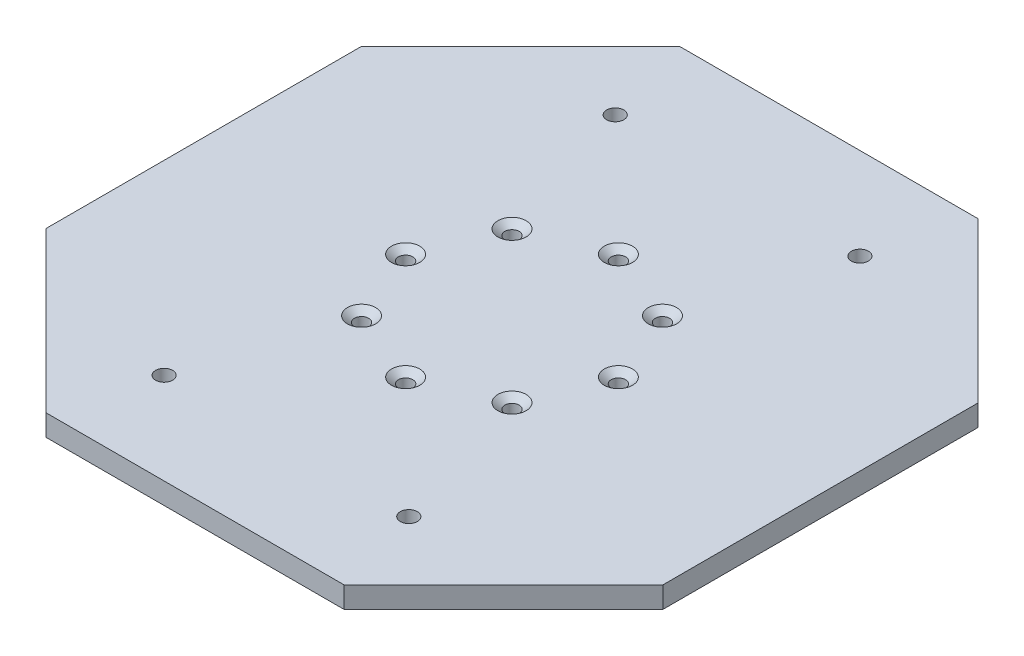
SolidWorks part; units mm, degrees
material "6061-T6 (SS)"
ref_plane "Front Plane" through (0, 0, 0) normal (0, 0, 1) x (1, 0, 0)
ref_plane "Top Plane" through (0, 0, 0) normal (0, 1, 0) x (1, 0, 0)
ref_plane "Right Plane" through (0, 0, 0) normal (1, 0, 0) x (0, 0, -1)
sketch "Sketch1" plane through (0, 0, 0) normal (0, 1, 0) x (1, 0, 0)
  line L0 (-92.075, 46.99) -> (-44.45, 94.615)
  line L1 (-44.45, -94.615) -> (44.45, -94.615)
  line L2 (-92.075, -46.99) -> (-92.075, 46.99)
  line L3 (-44.45, 94.615) -> (44.45, 94.615)
  line L4 (92.075, -46.99) -> (92.075, 46.99)
  line L5 (-85.725, -85.725) -> (85.725, 85.725) construction
  line L6 (-85.725, 85.725) -> (85.725, -85.725) construction
  line L7 (44.45, 94.615) -> (92.075, 46.99)
  line L8 (92.075, -46.99) -> (44.45, -94.615)
  line L9 (-92.075, -46.99) -> (-44.45, -94.615)
  line L11 (-38.1, 82.55) -> (38.1, 82.55) construction
  line L12 (-38.1, 82.55) -> (-38.1, 57.15) construction
  line L13 (-38.1, 57.15) -> (38.1, 57.15) construction
  line L14 (38.1, 82.55) -> (38.1, 57.15) construction
  line L15 (-38.1, 82.55) -> (38.1, 57.15) construction
  line L16 (-38.1, 57.15) -> (38.1, 82.55) construction
  line L17 (-44.45, 85.09) -> (44.45, 85.09) construction
  line L18 (-44.45, 85.09) -> (-44.45, 54.61) construction
  line L19 (-44.45, 54.61) -> (44.45, 54.61) construction
  line L20 (44.45, 85.09) -> (44.45, 54.61) construction
  line L21 (-44.45, 85.09) -> (44.45, 54.61) construction
  line L22 (-44.45, 54.61) -> (44.45, 85.09) construction
  circle A0 centre (0, 0) radius 38.1 construction
  circle A1 centre (0, 0) radius 50.8 construction
  point P0 (0, 0)
  point P17 (0, 69.85)
  point P22 (0, 69.85)
  point P27 (-92.075, 0)
  point P28 (0, 94.615)
  dimension "D4" = 76.2
  dimension "D5" = 101.6
  dimension "D1" = 171.45
  dimension "D2" = 171.45
  dimension "D3" = 88.9
  dimension "D6" = 2.54
  dimension "D7" = 25.4
  dimension "D8" = 76.2
  dimension "D9" = 88.9
  dimension "D10" = 6.35
  dimension "D11" = 189.23
  dimension "D12" = 184.15
extrude "Boss-Extrude1" add sketch "Sketch1" along normal blind 6.35
hole_wizard "#7 (0.201) Diameter Hole1" positions "Sketch3" profile "Sketch2" hole size "#7" standard "ANSI Inch" end condition through all
sketch "Sketch3" plane through (0, 6.35, 0) normal (0, 1, 0) x (-1, 0, 0)
  line L0 (-36.5125, -67.31) -> (0, 0) construction
  line L1 (0, 0) -> (36.5125, -67.31) construction
  line L5 (-873.478, -60.325) -> (49126.522, -60.325) construction
  point P0 (36.5125, -67.31)
  point P1 (-36.5125, -67.31)
  dimension "D1" = 73.025
  dimension "D2" = 60.325
  dimension "D3" = 6.985
sketch "Sketch2" plane through (-36.5125, 6.35, -67.31) normal (1, 0, 0) x (0, 0, 1)
  line L0 (0, 0) -> (0, 6.35)
  line L1 (0, 6.35) -> (2.5527, 6.35)
  line L2 (2.5527, 6.35) -> (2.5527, 0)
  line L5 (2.5527, 0) -> (0, 0)
  line L11 (0, -6.35) -> (0, 107.95) construction
  dimension "Thru Hole Dia." = 5.1054
  dimension "Thru Hole Depth" = 6.35
ref_axis "Axis1" through (0, 0, 0) along (0, 1, 0)
pattern_circular "CirPattern1" count 2 over 360 about axis through (0, 0, 0) along (0, 1, 0) of "#7 (0.201) Diameter Hole1"
hole_wizard "CSK for #8 Flat Head Machine Screw (100)1" positions "Sketch5" profile "Sketch4" countersink size "#8" standard "Ansi Inch" end condition through all
sketch "Sketch5" plane through (0, 6.35, 0) normal (0, 1, 0) x (-1, 0, 0)
  point P0 (0, 31.75)
  dimension "D1" = 31.75
sketch "Sketch4" plane through (0, 6.35, 31.75) normal (1, 0, 0) x (0, 0, 1)
  line L0 (0, 0) -> (0, 6.35)
  line L1 (0, 6.35) -> (2.1526, 6.35)
  line L2 (2.1526, 6.35) -> (2.1526, 1.7317)
  line L3 (2.1526, 1.7317) -> (4.2164, 0)
  line L5 (4.2164, 0) -> (0, 0)
  line L6 (-2.1526, 1.7317) -> (-4.2164, 0) construction
  line L11 (0, -6.35) -> (0, 107.95) construction
  dimension "Thru Hole Dia." = 4.3053
  dimension "Thru Hole Depth" = 6.35
  dimension "Near C'Sink Dia." = 8.4328
  dimension "Near C'Sink Angle" = 100
pattern_circular "CirPattern2" count 8 over 360 about axis through (0, 0, 0) along (0, 1, 0) of "CSK for #8 Flat Head Machine Screw (100)1"
